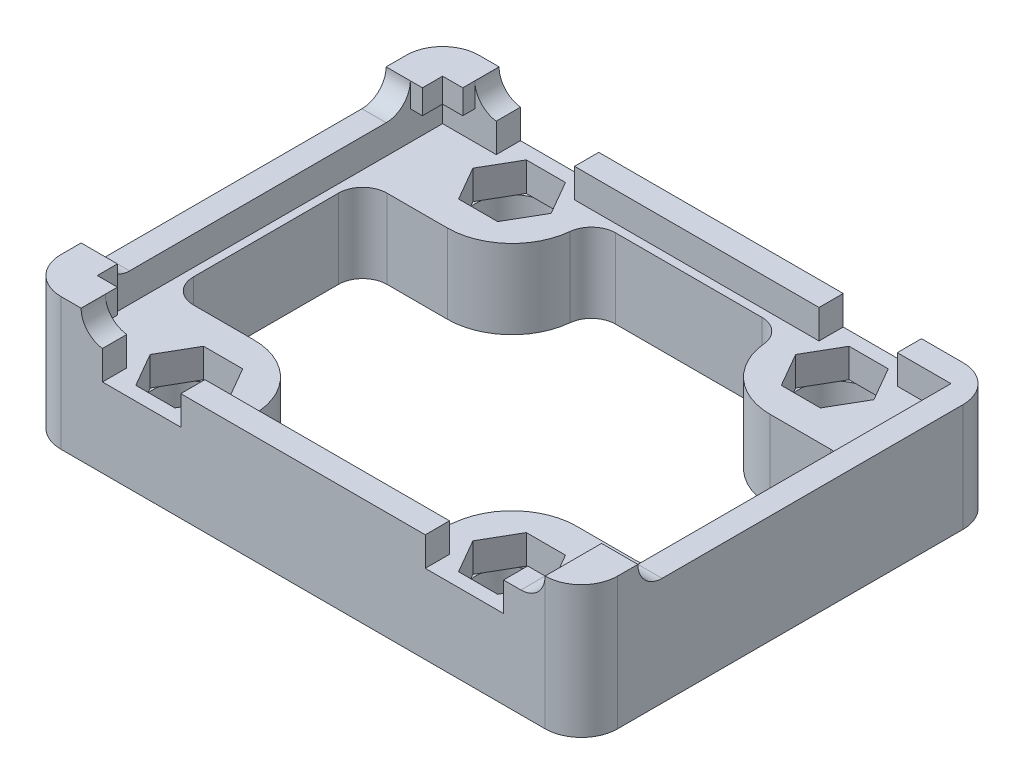
SolidWorks part; units mm, degrees
ref_plane "Front Plane" through (0, 0, 0) normal (0, 0, 1) x (1, 0, 0)
ref_plane "Top Plane" through (0, 0, 0) normal (0, 1, 0) x (1, 0, 0)
ref_plane "Right Plane" through (0, 0, 0) normal (1, 0, 0) x (0, 0, -1)
sketch "Sketch1" plane through (0, 0, 0) normal (0, 1, 0) x (1, 0, 0)
  line L0 (-15.75, 11.45) -> (-17.25, 11.45) construction
  line L1 (10, 10) -> (-10, 10)
  line L2 (10, 10) -> (10, -10)
  line L3 (10, -10) -> (-10, -10)
  line L4 (-10, 10) -> (-10, -10)
  line L5 (10, 10) -> (-10, -10) construction
  line L6 (10, -10) -> (-10, 10) construction
  line L7 (15.75, -11.45) -> (-15.75, -11.45)
  line L8 (15.75, -11.45) -> (15.75, 11.45)
  line L9 (15.75, 11.45) -> (-15.75, 11.45)
  line L10 (-15.75, -11.45) -> (-15.75, 11.45)
  line L11 (15.75, -11.45) -> (-15.75, 11.45) construction
  line L12 (15.75, 11.45) -> (-15.75, -11.45) construction
  line L13 (17.25, -12.95) -> (-17.25, -12.95)
  line L14 (17.25, -12.95) -> (17.25, 12.95)
  line L15 (17.25, 12.95) -> (-17.25, 12.95)
  line L16 (-17.25, -12.95) -> (-17.25, 12.95)
  line L17 (17.25, -12.95) -> (-17.25, 12.95) construction
  line L18 (17.25, 12.95) -> (-17.25, -12.95) construction
  line L19 (-15.75, 11.45) -> (-15.75, 12.95) construction
  circle A0 centre (-10, 10) radius 1.55
  circle A1 centre (10, 10) radius 1.55
  circle A2 centre (10, -10) radius 1.55
  circle A3 centre (-10, -10) radius 1.55
  point P0 (0, 0)
  point P10 (0, 0)
  point P15 (0, 0)
  dimension "D2" = 3.1
  dimension "D3" = 22.9
  dimension "D1" = 20
  dimension "D4" = 31.5
  dimension "D5" = 1.5
extrude "Boss-Extrude1" add sketch "Sketch1" along normal blind 1.5
sketch "Sketch3" plane through (0, 1.5, 0) normal (0, 1, 0) x (1, 0, 0)
  line L4 (17.25, -12.95) -> (17.25, 12.95)
  line L5 (17.25, 12.95) -> (-17.25, 12.95)
  line L6 (-17.25, 12.95) -> (-17.25, -12.95)
  line L7 (-17.25, -12.95) -> (17.25, -12.95)
  line L8 (17.25, -12.95) -> (17.25, 12.95)
  line L9 (17.25, 12.95) -> (-17.25, 12.95)
  line L10 (-17.25, 12.95) -> (-17.25, -12.95)
  line L11 (-17.25, -12.95) -> (17.25, -12.95)
  circle A0 centre (-10, 10) radius 2.25
  circle A1 centre (10, 10) radius 2.25
  circle A2 centre (10, -10) radius 2.25
  circle A3 centre (-10, -10) radius 2.25
  dimension "D1" = 4.5
  dimension "D2" = 0
extrude "Boss-Extrude3" add sketch "Sketch3" along normal blind 1.6
sketch "Sketch5" plane through (0, 3.1, 0) normal (0, 1, 0) x (1, 0, 0)
  line L0 (-15.25, -10.95) -> (15.25, -10.95)
  line L1 (-11.2124, 7.9) -> (-8.7876, 7.9)
  line L2 (-8.7876, 7.9) -> (-7.5751, 10)
  line L3 (-7.5751, 10) -> (-8.7876, 12.1)
  line L4 (-8.7876, 12.1) -> (-11.2124, 12.1)
  line L5 (-11.2124, 12.1) -> (-12.4249, 10)
  line L6 (-12.4249, 10) -> (-11.2124, 7.9)
  line L7 (15.25, -10.95) -> (15.25, 10.95)
  line L8 (15.25, 10.95) -> (-15.25, 10.95)
  line L9 (-15.25, 10.95) -> (-15.25, -10.95)
  line L10 (-17.25, -12.95) -> (17.25, -12.95)
  line L11 (17.25, -12.95) -> (17.25, 12.95)
  line L12 (17.25, 12.95) -> (-17.25, 12.95)
  line L13 (-17.25, 12.95) -> (-17.25, -12.95)
  line L14 (-17.25, -12.95) -> (17.25, -12.95)
  line L15 (17.25, -12.95) -> (17.25, 12.95)
  line L16 (17.25, 12.95) -> (-17.25, 12.95)
  line L17 (-17.25, 12.95) -> (-17.25, -12.95)
  line L18 (10, 6) -> (15.25, 6)
  line L19 (-6, 10) -> (-6, 10.95)
  line L20 (0, 12.95) -> (0, -12.95) construction
  line L21 (-17.25, 0) -> (17.25, 0) construction
  line L22 (-10, 6) -> (-15.25, 6)
  line L23 (6, 10) -> (6, 10.95)
  line L24 (11.2124, 7.9) -> (8.7876, 7.9)
  line L25 (12.4249, 10) -> (11.2124, 7.9)
  line L26 (11.2124, 12.1) -> (12.4249, 10)
  line L27 (8.7876, 12.1) -> (11.2124, 12.1)
  line L28 (7.5751, 10) -> (8.7876, 12.1)
  line L29 (8.7876, 7.9) -> (7.5751, 10)
  line L30 (-10, -6) -> (-15.25, -6)
  line L31 (-6, -10) -> (-6, -10.95)
  line L32 (-8.7876, -7.9) -> (-7.5751, -10)
  line L33 (-11.2124, -7.9) -> (-8.7876, -7.9)
  line L34 (-12.4249, -10) -> (-11.2124, -7.9)
  line L35 (-11.2124, -12.1) -> (-12.4249, -10)
  line L36 (-8.7876, -12.1) -> (-11.2124, -12.1)
  line L37 (-7.5751, -10) -> (-8.7876, -12.1)
  line L38 (6, -10) -> (6, -10.95)
  line L39 (10, -6) -> (15.25, -6)
  line L40 (11.2124, -12.1) -> (12.4249, -10)
  line L41 (8.7876, -12.1) -> (11.2124, -12.1)
  line L42 (7.5751, -10) -> (8.7876, -12.1)
  line L43 (8.7876, -7.9) -> (7.5751, -10)
  line L44 (11.2124, -7.9) -> (8.7876, -7.9)
  line L45 (12.4249, -10) -> (11.2124, -7.9)
  circle A0 centre (-10, 10) radius 2.1 construction
  circle A1 centre (-10, 10) radius 4
  circle A2 centre (10, 10) radius 4
  circle A3 centre (-10, -10) radius 4
  circle A4 centre (10, -10) radius 4
  dimension "D4" = 8
  dimension "D1" = 4.2
  dimension "D2" = 0
  dimension "D3" = 2
extrude "Boss-Extrude4" add sketch "Sketch5" along normal blind 1.8
sketch "Sketch6" plane through (0, 4.9, 0) normal (0, 1, 0) x (1, 0, 0)
  line L0 (-15.75, -11.45) -> (15.75, -11.45)
  line L1 (15.75, -11.45) -> (15.75, 11.45)
  line L2 (15.75, 11.45) -> (-15.75, 11.45)
  line L3 (-15.75, 11.45) -> (-15.75, -11.45)
  line L4 (-17.25, -12.95) -> (17.25, -12.95)
  line L5 (17.25, -12.95) -> (17.25, 12.95)
  line L6 (17.25, 12.95) -> (-17.25, 12.95)
  line L7 (-17.25, 12.95) -> (-17.25, -12.95)
  line L8 (-17.25, -12.95) -> (17.25, -12.95)
  line L9 (17.25, -12.95) -> (17.25, 12.95)
  line L10 (17.25, 12.95) -> (-17.25, 12.95)
  line L11 (-17.25, 12.95) -> (-17.25, -12.95)
  line L12 (-10, 10) -> (-10, -10) construction
  line L13 (0, 12.95) -> (0, -12.95) construction
  line L14 (-7.5751, -12.95) -> (-12.4249, -12.95)
  line L15 (-7.5751, -12.95) -> (-7.5751, 12.95)
  line L16 (-7.5751, 12.95) -> (-12.4249, 12.95)
  line L17 (-12.4249, -12.95) -> (-12.4249, 12.95)
  line L18 (-7.5751, -12.95) -> (-12.4249, 12.95) construction
  line L19 (-7.5751, 12.95) -> (-12.4249, -12.95) construction
  line L20 (7.5751, -12.95) -> (12.4249, -12.95)
  line L21 (12.4249, -12.95) -> (12.4249, 12.95)
  line L22 (7.5751, 12.95) -> (12.4249, 12.95)
  line L23 (7.5751, -12.95) -> (7.5751, 12.95)
  point P10 (-10, 0)
  line M37 (-17.25, -12.95) -> (17.25, -12.95)
  line M38 (17.25, -12.95) -> (17.25, 12.95)
  line M39 (17.25, 12.95) -> (-17.25, 12.95)
  line M40 (-17.25, 12.95) -> (-17.25, -12.95)
  dimension "D1" = 0
  dimension "D2" = 1.5
extrude "Boss-Extrude5" add sketch "Sketch6" along normal blind 1.8 contours L17 L0 L3 L2 M37 M39 M40 | L2 L23 L15 M39 | L21 L2 L1 L0 M37 M38 M39 | L23 L0 L15 M37
sketch "Sketch7" plane through (0, 6.7, 0) normal (0, 1, 0) x (1, 0, 0)
  line L0 (-15.75, 11.45) -> (-15.75, -11.45) construction
  line L1 (-17.25, 12.95) -> (17.25, 12.95)
  line L2 (-17.25, 12.95) -> (-17.25, -12.95)
  line L3 (-17.25, -12.95) -> (17.25, -12.95)
  line L4 (17.25, 12.95) -> (17.25, -12.95)
  line L5 (15, -10.7) -> (-15, -10.7)
  line L6 (15, -10.7) -> (15, 10.7)
  line L7 (15, 10.7) -> (-15, 10.7)
  line L8 (-15, -10.7) -> (-15, 10.7)
  line L9 (15, -10.7) -> (-15, 10.7) construction
  line L10 (15, 10.7) -> (-15, -10.7) construction
  line L11 (-15, 10.7) -> (-15.75, 10.7) construction
  line L12 (-15.75, 11.45) -> (-15.75, -11.45) construction
  line L13 (-15, 10.7) -> (-15, 11.45) construction
  line L14 (-12.4249, 11.45) -> (-15.75, 11.45) construction
  line L16 (-17.25, 12.95) -> (-13.75, 12.95)
  line L17 (-17.25, 12.95) -> (-17.25, 9.45)
  line L18 (-17.25, 9.45) -> (-13.75, 9.45)
  line L19 (-13.75, 12.95) -> (-13.75, 9.45)
  line L20 (-17.25, 0) -> (17.25, 0) construction
  line L21 (-17.25, -12.95) -> (-13.75, -12.95)
  line L22 (-13.75, -12.95) -> (-13.75, -9.45)
  line L23 (-17.25, -9.45) -> (-13.75, -9.45)
  line L24 (-17.25, -12.95) -> (-17.25, -9.45)
  line L27 (17.25, -12.95) -> (15, -12.95)
  line L28 (17.25, -12.95) -> (17.25, -9.45)
  line L29 (17.25, -9.45) -> (15, -9.45)
  line L30 (15, -12.95) -> (15, -9.45)
  point P6 (0, 0)
  line M24 (-17.25, -12.95) -> (-12.4249, -12.95)
  line M26 (-12.4249, -11.45) -> (-15.75, -11.45)
  line M27 (-15.75, -11.45) -> (-15.75, 11.45)
  line M28 (-15.75, 11.45) -> (-12.4249, 11.45)
  line M31 (-17.25, 12.95) -> (-17.25, -12.95)
  dimension "D1" = 0.75
  dimension "D2" = 2
extrude "Boss-Extrude6" add sketch "Sketch7" along normal blind 1.5 contours L19 L1 L18 M31 M27 M28 | L19 L18 L8 L7 M28 M27 | L23 L22 M31 M24 M26 M27 | L23 L22 L5 L8 M27 M26 | L30 L3 L4 L29 L6
sketch "Sketch8" plane through (0, 3.1, 0) normal (0, 1, 0) x (1, 0, 0)
  line L12 (10, -6) -> (15.25, -6)
  line L13 (10, -6) -> (15.25, -6)
  line L14 (15.25, 6) -> (10, 6)
  line L15 (15.25, 6) -> (10, 6)
  line L16 (-10, 6) -> (-15.25, 6)
  line L17 (-6, -10.95) -> (6, -10.95)
  line L18 (15.25, -6) -> (15.25, 6)
  line L19 (6, 10.95) -> (-6, 10.95)
  line L20 (-10, 6) -> (-15.25, 6)
  line L21 (6, 10) -> (6, 10.95)
  line L22 (-15.25, -6) -> (-10, -6)
  line L23 (-6, 10.95) -> (-6, 10)
  line L24 (-15.25, -6) -> (-10, -6)
  line L26 (-15.25, 6) -> (-15.25, -6)
  line L29 (-6, -10) -> (-6, -10.95)
  line L31 (6, -10.95) -> (6, -10)
  line L33 (-6, -10.95) -> (6, -10.95)
  line L34 (15.25, -6) -> (15.25, 6)
  line L35 (6, 10.95) -> (-6, 10.95)
  line L37 (6, 10) -> (6, 10.95)
  line L39 (-6, 10.95) -> (-6, 10)
  line L42 (-15.25, 6) -> (-15.25, -6)
  line L45 (-6, -10) -> (-6, -10.95)
  line L47 (6, -10.95) -> (6, -10)
  arc A4 (6, 10) -> (10, 6) centre (10, 10) ccw
  arc A5 (-10, 6) -> (-6, 10) centre (-10, 10) ccw
  arc A6 (-6, -10) -> (-10, -6) centre (-10, -10) ccw
  arc A7 (10, -6) -> (6, -10) centre (10, -10) ccw
  arc A8 (6, 10) -> (10, 6) centre (10, 10) ccw
  arc A9 (-10, 6) -> (-6, 10) centre (-10, 10) ccw
  arc A10 (-6, -10) -> (-10, -6) centre (-10, -10) ccw
  arc A11 (10, -6) -> (6, -10) centre (10, -10) ccw
  dimension "D1" = 0
extrude "Cut-Extrude1" cut sketch "Sketch8" against normal up to next
fillet "Fillet1" radius 1.5 14 edges at (6, 2.45, 10.95) (15.25, 2.45, 6) (15.25, 2.45, -6) (6, 2.45, -10.95) (-6, 2.45, -10.95) (-15.25, 2.45, -6) (-15.25, 2.45, 6) (-6, 2.45, 10.95) (16.5, 6.7, 9.45) (15, 6.7, 12.2) (-13.75, 6.7, -12.2) (-16.5, 6.7, 9.45) (-13.75, 6.7, 12.2) (-16.5, 6.7, -9.45)
fillet "Fillet2" radius 2.25 4 edges at (17.25, 3.35, -12.95) (17.25, 4.1, 12.95) (-17.25, 4.1, -12.95) (-17.25, 4.1, 12.95)
